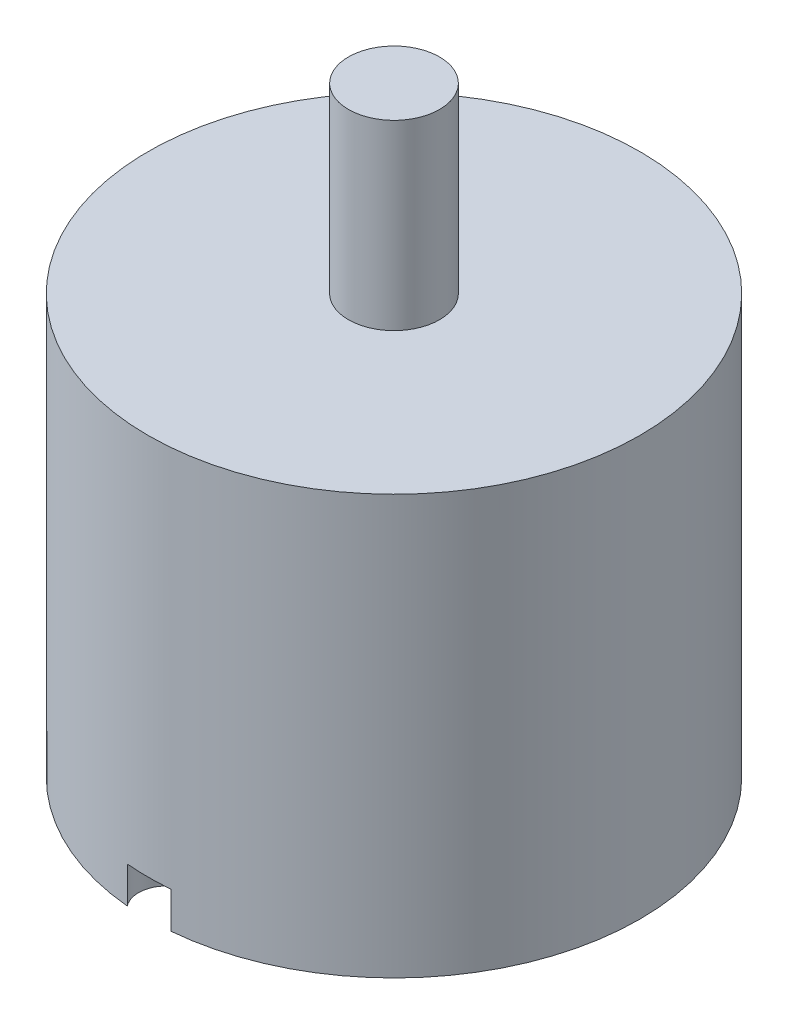
SolidWorks part; units mm, degrees
ref_plane "Front Plane" through (0, 0, 0) normal (0, 0, 1) x (1, 0, 0)
ref_plane "Top Plane" through (0, 0, 0) normal (0, 1, 0) x (1, 0, 0)
ref_plane "Right Plane" through (0, 0, 0) normal (1, 0, 0) x (0, 0, -1)
sketch "Sketch1" plane through (0, 0, 0) normal (0, 1, 0) x (1, 0, 0)
  circle A0 centre (0, 0) radius 13.5
  dimension "D1" = 26.9999
extrude "Boss-Extrude1" add sketch "Sketch1" along normal blind 23
sketch "Sketch2" plane through (0, 23, 0) normal (0, 1, 0) x (1, 0, 0)
  circle A0 centre (0, 0) radius 2.5
  dimension "D1" = 5
extrude "Boss-Extrude2" add sketch "Sketch2" along normal blind 10
sketch "Sketch3" plane through (0, 0, 0) normal (0, -1, 0) x (1, 0, 0)
  circle A0 centre (0, 0) radius 1.627
  dimension "D1" = 3.254
extrude "Boss-Extrude3" add sketch "Sketch3" along normal blind 2
sketch "Sketch4" plane through (0, 0, 0) normal (0, -1, 0) x (1, 0, 0)
  line L0 (0, 0) -> (0, 8.6454) construction
  line L1 (0, 0) -> (7.4808, 0) construction
  circle A0 centre (0, 12.5) radius 1.524
  circle A1 centre (9.5, 0) radius 1.5
  circle A2 centre (-9.5, 0) radius 1.5
  circle A3 centre (0, -12.5) radius 1.524
  dimension "D1" = 3.048
  dimension "D2" = 3
  dimension "D3" = 9.5
  dimension "D4" = 12.5
extrude "Cut-Extrude1" cut sketch "Sketch4" against normal blind 2
equation "\"Motor Y\"= \"Motor Screw Y@Quad Assemb.sldasm\""
equation "\"D4@Sketch4\"=\"Motor Y\"/2"
equation "\"Motor X\"= \"Motor Screw X@Quad Assemb.sldasm\""
equation "\"D3@Sketch4\"=\"Motor X\"/2"
equation "\"Motor Diam\"= \"Motor Diam@Quad Assemb.sldasm\""
equation "\"D1@Sketch1\"=\"Motor Diam\""
equation "\"D1@Boss-Extrude1\"=\"Motor Length@Quad Assemb.sldasm\""
equation "\"D1@Sketch3\"=\"motor shaft diam@quad assemb.sldasm\""
